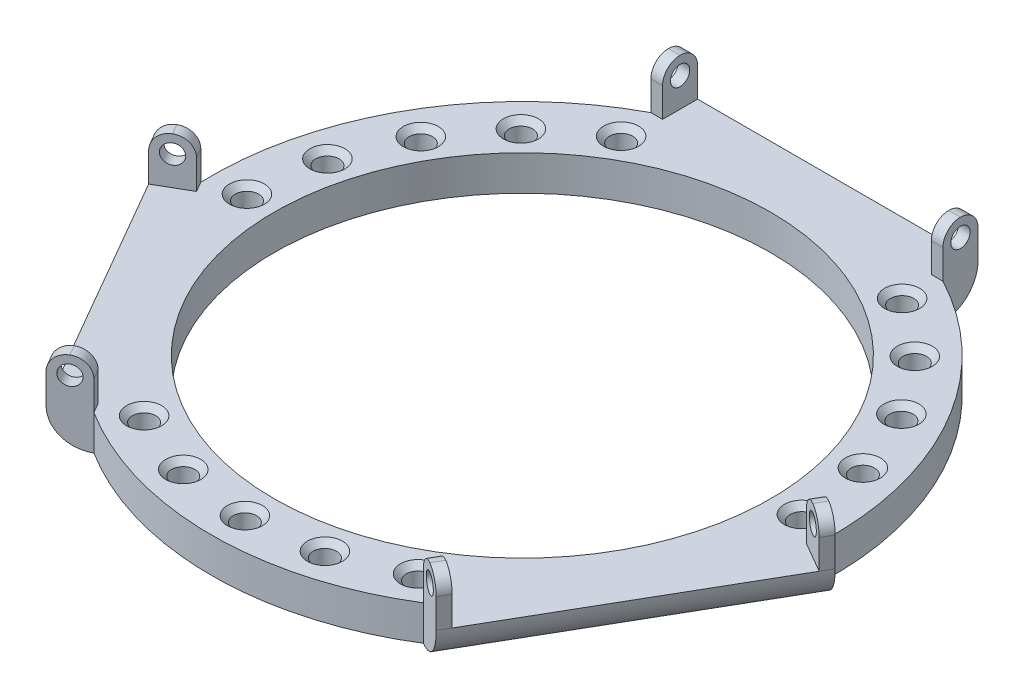
SolidWorks part; units mm, degrees
ref_plane "Front Plane" through (0, 0, 0) normal (0, 0, 1) x (1, 0, 0)
ref_plane "Top Plane" through (0, 0, 0) normal (0, 1, 0) x (1, 0, 0)
ref_plane "Right Plane" through (0, 0, 0) normal (1, 0, 0) x (0, 0, -1)
sketch "Sketch1" plane through (0, 0, 0) normal (0, 1, 0) x (1, 0, 0)
  line L0 (0, 0) -> (0, 50) construction
  line L1 (-23, 47) -> (-25, 47)
  line L2 (-23, 47) -> (-23, 53)
  line L3 (-23, 53) -> (-25, 53)
  line L4 (-25, 47) -> (-25, 53)
  line L5 (23, 47) -> (25, 47)
  line L6 (23, 47) -> (23, 53)
  line L7 (23, 53) -> (25, 53)
  line L8 (25, 47) -> (25, 53)
  line L9 (25, 50) -> (-25, 50) construction
  circle A0 centre (0, 0) radius 50 construction
  dimension "D1" = 2
  dimension "D2" = 6
  dimension "D3" = 50
  dimension "D4" = 50
extrude "Boss-Extrude1" add sketch "Sketch1" along normal blind 8
sketch "Sketch2" plane through (0, 0, 0) normal (0, 1, 0) x (1, 0, 0)
  line L0 (0, 0) -> (0, 53.2353) construction
  line L1 (46.1031, 26.6177) -> (0, 0) construction
  line L2 (0, 0) -> (-46.1031, 26.6177) construction
  line L3 (25, 53) -> (-25, 53)
  line L4 (-25, 53) -> (-25, 47) construction
  line L5 (25, 47) -> (25, 53) construction
  line L6 (-25, 53) -> (-25, 47)
  line L7 (25, 47) -> (25, 53)
  line L8 (36.8061, 21.25) -> (46.1031, 26.6177)
  line L9 (-36.8061, 21.25) -> (-46.1031, 26.6177)
  arc A0 (-25, 47) -> (-46.1031, 26.6177) centre (0, 0) ccw
  arc A1 (36.8061, 21.25) -> (-36.8061, 21.25) centre (0, 0) ccw
  arc A2 (5, 53) -> (-5, 53) centre (0, 0) ccw construction
  arc A3 (46.1031, 26.6177) -> (25, 47) centre (0, 0) ccw
  dimension "D1" = 60
  dimension "D2" = 85
extrude "Boss-Extrude2" add sketch "Sketch2" against normal blind 6
fillet "Fillet2" radius 3 4 edges at (24, 8, -47) (24, 8, -53) (-24, 8, -47) (-24, 8, -53)
sketch "Sketch3" plane through (25, 0, 0) normal (1, 0, 0) x (0, 0, -1)
  circle A0 centre (50, 5) radius 1.65
  arc A1 (53, 5) -> (50, 8) centre (50, 5) ccw construction
  dimension "D1" = 3.3
extrude "Cut-Extrude1" cut sketch "Sketch3" against normal through all
fillet "Fillet3" radius 6 1 edges at (0, -6, -53)
pattern_circular "CirPattern2" count 3 over 360 about axis through (0, -6, 0) along (0, -1, 0) of "Boss-Extrude2", "Fillet2", "Cut-Extrude1", "Fillet3", "Boss-Extrude1"
sketch "Sketch4" plane through (0, 0, 0) normal (0, 1, 0) x (1, 0, 0)
  line L0 (-47.4987, 0.3501) -> (-45.8359, 12.4629) construction
  line L1 (-45.8359, 12.4629) -> (-41.1362, 23.75) construction
  line L2 (-41.1362, 23.75) -> (-33.7111, 33.4636) construction
  line L3 (-33.7111, 33.4636) -> (-24.0526, 40.96) construction
  line L4 (0, 0) -> (-25, 47) construction
  line L5 (0, 0) -> (-53.2032, -1.8494) construction
  circle A0 centre (0, 0) radius 47.5 construction
  circle A2 centre (-41.1362, 23.75) radius 2
  circle A3 centre (-24.0526, 40.96) radius 2
  circle A4 centre (-47.4987, 0.3501) radius 2
  circle A5 centre (-33.7111, 33.4636) radius 2
  circle A6 centre (-45.8359, 12.4629) radius 2
  circle A7 centre (47.4987, 0.3501) radius 2
  circle A8 centre (45.8359, 12.4629) radius 2
  circle A9 centre (41.1362, 23.75) radius 2
  circle A10 centre (33.7111, 33.4636) radius 2
  circle A11 centre (24.0526, 40.96) radius 2
  circle A12 centre (-23.4461, -41.3102) radius 2
  circle A13 centre (-12.1247, -45.9265) radius 2
  circle A14 centre (0, -47.5) radius 2
  circle A15 centre (12.1247, -45.9265) radius 2
  circle A16 centre (23.4461, -41.3102) radius 2
  point P52 (0, 0)
  dimension "D1" = 95
  dimension "D2" = 4
  dimension "D3" = 3
extrude "Cut-Extrude2" cut sketch "Sketch4" against normal through all
chamfer "Chamfer1" distance 1 angle 45 15 edges at (-23.4461, 0, 43.3102) (-12.1247, 0, 47.9265) (0, 0, 49.5) (12.1247, 0, 47.9265) (23.4461, 0, 43.3102) (47.4987, 0, 1.6499) (45.8359, 0, -10.4629) (41.1362, 0, -21.75) (33.7111, 0, -31.4636) (24.0526, 0, -38.96) (-24.0526, 0, -38.96) (-33.7111, 0, -31.4636) (-41.1362, 0, -21.75) (-45.8359, 0, -10.4629) (-47.4987, 0, 1.6499)
